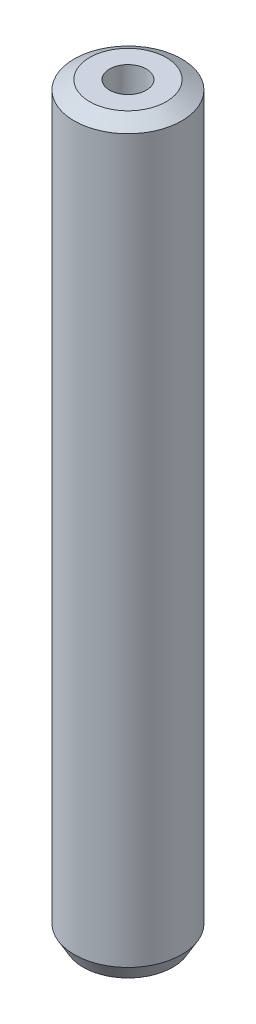
SolidWorks part; units mm, degrees
ref_plane "Front Plane" through (0, 0, 0) normal (0, 0, 1) x (1, 0, 0)
ref_plane "Top Plane" through (0, 0, 0) normal (0, 1, 0) x (1, 0, 0)
ref_plane "Right Plane" through (0, 0, 0) normal (1, 0, 0) x (0, 0, -1)
sketch "Sketch1" plane through (0, 0, 0) normal (0, 1, 0) x (1, 0, 0)
  circle A0 centre (0, 0) radius 15
  dimension "SHAFT_OD" = 30
extrude "Boss-Extrude1" add sketch "Sketch1" along normal blind 208.2812
sketch "Sketch2" plane through (0, 0, 0) normal (0, 1, 0) x (1, 0, 0)
  circle A0 centre (0, 0) radius 5.1278
  dimension "BORE_D" = 10.2556
extrude "Cut-Extrude1" cut sketch "Sketch2" along normal through all
chamfer "Chamfer1" distance 2.4915 angle 60 2 edges at (0, 208.2812, 15) (0, 0, 15) first distance on face at (0, 208.2812, 15) first distance on face at (0, 0, 5.1278)
